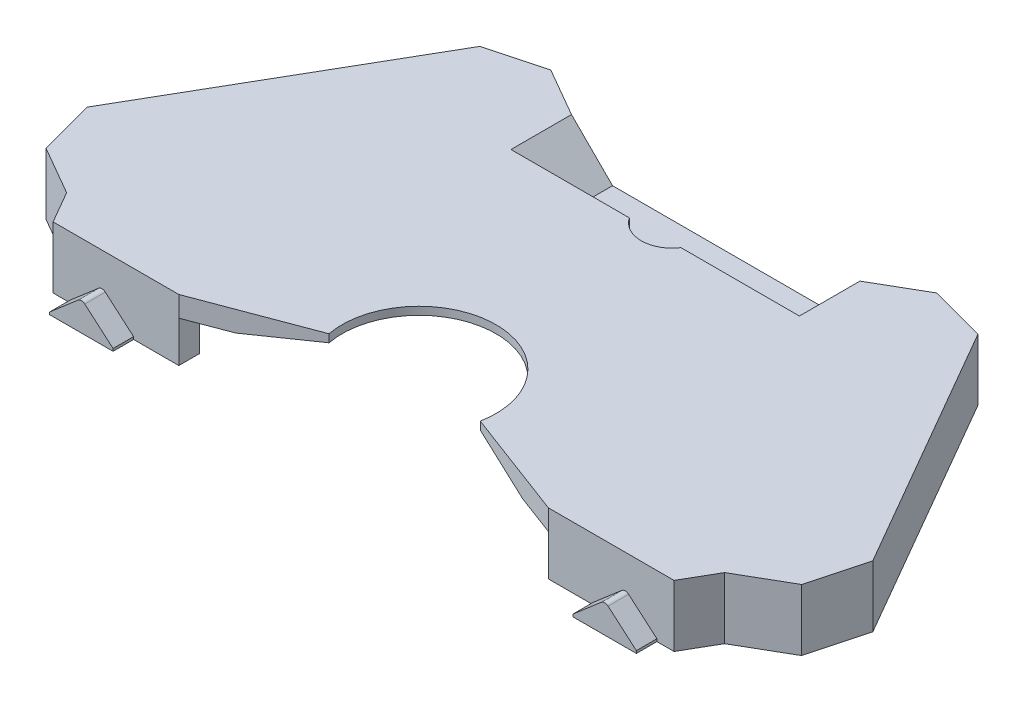
SolidWorks part; units mm, degrees
ref_plane "Front Plane" through (0, 0, 0) normal (0, 0, 1) x (1, 0, 0)
ref_plane "Top Plane" through (0, 0, 0) normal (0, 1, 0) x (1, 0, 0)
ref_plane "Right Plane" through (0, 0, 0) normal (1, 0, 0) x (0, 0, -1)
sketch "Sketch1" plane through (0, 0, 0) normal (0, 1, 0) x (1, 0, 0)
  line L0 (-33, 19.0526) -> (33, 19.0526) construction
  line L1 (33, 19.0526) -> (0, -38.1051) construction
  line L2 (0, -38.1051) -> (-33, 19.0526) construction
  line L3 (-43, 1.7321) -> (-23, 36.3731) construction
  line L4 (23, 36.3731) -> (43, 1.7321) construction
  line L5 (20, -38.1051) -> (-20, -38.1051) construction
  line L6 (-23, 36.3731) -> (-13.5115, 30.8949) construction
  line L7 (-13.5115, 30.8949) -> (13.5115, 30.8949) construction
  line L8 (13.5115, 30.8949) -> (23, 36.3731) construction
  line L9 (-43, 1.7321) -> (-33.5115, -3.7461) construction
  line L10 (-33.5115, -3.7461) -> (-20, -27.1487) construction
  line L11 (-20, -27.1487) -> (-20, -38.1051) construction
  line L12 (20, -38.1051) -> (20, -27.1487) construction
  line L13 (20, -27.1487) -> (33.5115, -3.7461) construction
  line L14 (33.5115, -3.7461) -> (43, 1.7321) construction
  line L15 (0, 26.3949) -> (0, 30.8949) construction
  line L16 (-17, 19.8949) -> (17, 19.8949) construction
  line L17 (-17, 19.8949) -> (-17, -1.1051) construction
  line L18 (17, 19.8949) -> (17, -1.1051) construction
  line L19 (-17, -1.1051) -> (-13, -1.1051) construction
  line L20 (-13, -1.1051) -> (-13, -12.1051) construction
  line L21 (-13, -12.1051) -> (13, -12.1051) construction
  line L22 (13, -12.1051) -> (13, -1.1051) construction
  line L23 (13, -1.1051) -> (17, -1.1051) construction
  line L24 (-27.6088, -13.9699) -> (-18.5155, -8.7199) construction
  line L25 (0, 0) -> (0, 19.0526) construction
  line L26 (-28, 22.3949) -> (-20, 22.3949) construction
  line L27 (-28, 22.3949) -> (-28, -5.6051) construction
  line L28 (-28, -5.6051) -> (-20, -5.6051) construction
  line L29 (-20, 22.3949) -> (-20, -5.6051) construction
  line L34 (28, -5.6051) -> (20, -5.6051) construction
  line L35 (20, 22.3949) -> (20, -5.6051) construction
  line L36 (28, 22.3949) -> (20, 22.3949) construction
  line L37 (28, 22.3949) -> (28, -5.6051) construction
  circle A0 centre (0, 0) radius 19.0526 construction
  circle A1 centre (0, 24.6449) radius 1.75 construction
  circle A2 centre (-17, -7.8449) radius 1.75 construction
  circle A3 centre (17, -7.8449) radius 1.75 construction
  point P4 (0, 19.0526)
  point P13 (0, -38.1051)
  point P15 (-33, 19.0526)
  point P17 (33, 19.0526)
  point P28 (0, 19.8949)
  dimension "D4" = 3.5
  dimension "D1" = 40
  dimension "D2" = 66
  dimension "D3" = 69
  dimension "D5" = 4.5
  dimension "D6" = 11
  dimension "D7" = 34
  dimension "D8" = 21
  dimension "D9" = 26
  dimension "D10" = 32
  dimension "D11" = 10.5
  dimension "D12" = 3
  dimension "D13" = 28
  dimension "D14" = 8
  dimension "D15" = 2.5
sketch "Sketch2" plane through (0, 0, 0) normal (0, 1, 0) x (1, 0, 0)
  line L0 (-17, 19.8949) -> (17, 19.8949) construction
  line L1 (17, 19.8949) -> (17, -1.1051) construction
  line L2 (13, -1.1051) -> (17, -1.1051) construction
  line L3 (13, -12.1051) -> (13, -1.1051) construction
  line L4 (-13, -12.1051) -> (13, -12.1051) construction
  line L5 (-13, -1.1051) -> (-13, -12.1051) construction
  line L6 (-17, -1.1051) -> (-13, -1.1051) construction
  line L7 (-17, 19.8949) -> (-17, -1.1051) construction
  line L8 (-28, -5.6051) -> (-20, -5.6051) construction
  line L9 (-28, 22.3949) -> (-28, -5.6051) construction
  line L10 (-20, 22.3949) -> (-20, -5.6051) construction
  line L11 (-28, 22.3949) -> (-20, 22.3949) construction
  line L12 (28, 22.3949) -> (20, 22.3949) construction
  line L13 (20, 22.3949) -> (20, -5.6051) construction
  line L14 (28, 22.3949) -> (28, -5.6051) construction
  line L15 (28, -5.6051) -> (20, -5.6051) construction
  line L16 (-23, 36.3731) -> (-13.5115, 30.8949) construction
  line L17 (-13.5115, 30.8949) -> (13.5115, 30.8949) construction
  line L18 (13.5115, 30.8949) -> (23, 36.3731) construction
  line L19 (23, 36.3731) -> (43, 1.7321) construction
  line L20 (33.5115, -3.7461) -> (43, 1.7321) construction
  line L21 (20, -27.1487) -> (33.5115, -3.7461) construction
  line L22 (20, -38.1051) -> (20, -27.1487) construction
  line L23 (20, -38.1051) -> (-20, -38.1051) construction
  line L24 (-20, -27.1487) -> (-20, -38.1051) construction
  line L25 (-33.5115, -3.7461) -> (-20, -27.1487) construction
  line L26 (-43, 1.7321) -> (-33.5115, -3.7461) construction
  line L27 (-43, 1.7321) -> (-23, 36.3731) construction
  line L28 (-15.5, 19.8949) -> (15.5, 19.8949)
  line L29 (17, 18.3949) -> (17, 0.3949)
  line L30 (15.1, -1.1051) -> (15.5, -1.1051)
  line L31 (13, -10.6051) -> (13, -3.2051)
  line L32 (-11.5, -12.1051) -> (11.5, -12.1051)
  line L33 (-13, -3.2051) -> (-13, -10.6051)
  line L34 (-15.5, -1.1051) -> (-15.1, -1.1051)
  line L35 (-17, 18.3949) -> (-17, 0.3949)
  line L36 (-26.5, -5.6051) -> (-21.5, -5.6051)
  line L37 (-28, 20.8949) -> (-28, -4.1051)
  line L38 (-20, 20.8949) -> (-20, -4.1051)
  line L39 (-26.5, 22.3949) -> (-21.5, 22.3949)
  line L40 (26.5, 22.3949) -> (21.5, 22.3949)
  line L41 (20, 20.8949) -> (20, -4.1051)
  line L42 (28, 20.8949) -> (28, -4.1051)
  line L43 (26.5, -5.6051) -> (21.5, -5.6051)
  line L44 (-21.5278, 35.5231) -> (-17.65, 33.2842)
  line L45 (-13.5115, 30.8949) -> (13.5115, 30.8949)
  line L46 (17.65, 33.2842) -> (21.5278, 35.5231)
  line L47 (23.85, 34.9008) -> (42.15, 3.2043)
  line L48 (37.65, -1.3568) -> (41.5278, 0.8821)
  line L49 (20, -27.1487) -> (33.5115, -3.7461)
  line L50 (20, -36.4051) -> (20, -31.9275)
  line L51 (18.3, -38.1051) -> (-18.3, -38.1051)
  line L52 (-20, -31.9275) -> (-20, -36.4051)
  line L53 (-33.5115, -3.7461) -> (-20, -27.1487)
  line L54 (-41.5278, 0.8821) -> (-37.65, -1.3568)
  line L55 (-42.15, 3.2043) -> (-23.85, 34.9008)
  line L56 (-13.5115, 30.8949) -> (-16.15, 30.8949)
  line L57 (-17.65, 32.3949) -> (-17.65, 33.2842)
  line L58 (13.5115, 30.8949) -> (16.15, 30.8949)
  line L59 (17.65, 32.3949) -> (17.65, 33.2842)
  line L60 (33.5115, -3.7461) -> (34.8308, -1.4611)
  line L61 (36.8798, -0.9121) -> (37.65, -1.3568)
  line L62 (20, -27.1487) -> (18.6808, -29.4338)
  line L63 (19.2298, -31.4828) -> (20, -31.9275)
  line L64 (-20, -27.1487) -> (-18.6808, -29.4338)
  line L65 (-19.2298, -31.4828) -> (-20, -31.9275)
  line L66 (-33.5115, -3.7461) -> (-34.8308, -1.4611)
  line L67 (-36.8798, -0.9121) -> (-37.65, -1.3568)
  line L68 (-23.85, 34.9008) -> (-21.5278, 35.5231)
  line L69 (-41.5278, 0.8821) -> (-42.15, 3.2043)
  line L70 (-20, -36.4051) -> (-18.3, -38.1051)
  line L71 (20, -36.4051) -> (18.3, -38.1051)
  line L72 (41.5278, 0.8821) -> (42.15, 3.2043)
  line L73 (21.5278, 35.5231) -> (23.85, 34.9008)
  line L74 (-15.1, -1.1051) -> (-13, -3.2051)
  line L75 (13, -3.2051) -> (15.1, -1.1051)
  circle A0 centre (17, -7.8449) radius 1.75 construction
  circle A1 centre (-17, -7.8449) radius 1.75 construction
  circle A2 centre (0, 24.6449) radius 1.75 construction
  circle A3 centre (17, -7.8449) radius 1.75
  circle A4 centre (-17, -7.8449) radius 1.75
  circle A5 centre (0, 24.6449) radius 1.75
  arc A6 (36.8798, -0.9121) -> (34.8308, -1.4611) centre (36.1298, -2.2111) ccw
  arc A7 (19.2298, -31.4828) -> (18.6808, -29.4338) centre (19.9798, -30.1838) cw
  arc A8 (-19.2298, -31.4828) -> (-18.6808, -29.4338) centre (-19.9798, -30.1838) ccw
  arc A9 (-36.8798, -0.9121) -> (-34.8308, -1.4611) centre (-36.1298, -2.2111) cw
  arc A10 (17.65, 32.3949) -> (16.15, 30.8949) centre (16.15, 32.3949) cw
  arc A11 (-17.65, 32.3949) -> (-16.15, 30.8949) centre (-16.15, 32.3949) ccw
  arc A12 (13, -10.6051) -> (11.5, -12.1051) centre (11.5, -10.6051) cw
  arc A13 (-13, -10.6051) -> (-11.5, -12.1051) centre (-11.5, -10.6051) ccw
  arc A14 (15.5, -1.1051) -> (17, 0.3949) centre (15.5, 0.3949) ccw
  arc A15 (-15.5, -1.1051) -> (-17, 0.3949) centre (-15.5, 0.3949) cw
  arc A16 (15.5, 19.8949) -> (17, 18.3949) centre (15.5, 18.3949) cw
  arc A17 (-15.5, 19.8949) -> (-17, 18.3949) centre (-15.5, 18.3949) ccw
  arc A18 (20, -4.1051) -> (21.5, -5.6051) centre (21.5, -4.1051) ccw
  arc A19 (28, -4.1051) -> (26.5, -5.6051) centre (26.5, -4.1051) cw
  arc A20 (26.5, 22.3949) -> (28, 20.8949) centre (26.5, 20.8949) cw
  arc A21 (21.5, 22.3949) -> (20, 20.8949) centre (21.5, 20.8949) ccw
  arc A22 (-28, -4.1051) -> (-26.5, -5.6051) centre (-26.5, -4.1051) ccw
  arc A23 (-21.5, -5.6051) -> (-20, -4.1051) centre (-21.5, -4.1051) ccw
  arc A24 (-20, 20.8949) -> (-21.5, 22.3949) centre (-21.5, 20.8949) ccw
  arc A25 (-26.5, 22.3949) -> (-28, 20.8949) centre (-26.5, 20.8949) ccw
  dimension "D2" = 1.5
  dimension "D3" = 1.5
  dimension "D1" = 35.3
  dimension "D4" = 1.7
  dimension "D5" = 45
  dimension "D6" = 1.7
  dimension "D7" = 45
  dimension "D8" = 1.7
  dimension "D9" = 45
  dimension "D10" = 1.7
  dimension "D11" = 45
  dimension "D12" = 1.7
  dimension "D13" = 45
  dimension "D14" = 1.7
  dimension "D15" = 45
  dimension "D16" = 2.1
  dimension "D17" = 45
  dimension "D18" = 2.1
  dimension "D19" = 45
extrude "Boss-Extrude1" [suppressed] add sketch "Sketch2" along normal blind 6
sketch "Sketch3" [suppressed] plane through (0, 6, 0) normal (0, 1, 0) x (1, 0, 0)
  line L0 (0, 0) -> (0, 28.3949) construction
  line L1 (-19.25, 28.3949) -> (19.25, 28.3949)
  line L2 (-20.75, 26.8949) -> (-20.75, -11.6051)
  line L3 (-19.25, -13.1051) -> (19.25, -13.1051)
  line L4 (20.75, 26.8949) -> (20.75, -11.6051)
  line L5 (16.15, 30.8949) -> (-16.15, 30.8949) construction
  arc A0 (20.75, -11.6051) -> (19.25, -13.1051) centre (19.25, -11.6051) cw
  arc A1 (-20.75, -11.6051) -> (-19.25, -13.1051) centre (-19.25, -11.6051) ccw
  arc A2 (19.25, 28.3949) -> (20.75, 26.8949) centre (19.25, 26.8949) cw
  arc A3 (-19.25, 28.3949) -> (-20.75, 26.8949) centre (-19.25, 26.8949) ccw
  point P15 (20.75, 28.3949)
  point P18 (-20.75, 28.3949)
  dimension "D3" = 1.5
  dimension "D1" = 41.5
  dimension "D2" = 2.5
extrude "Cut-Extrude1" [suppressed] cut sketch "Sketch3" against normal blind 1.4 contours L2 A1 L3 A0 L4 A2 L1 A3
sketch "Sketch4" [suppressed] plane through (0, 0, 0) normal (0, 1, 0) x (1, 0, 0)
  line L0 (28, -5.6051) -> (20, -5.6051) construction
  line L1 (28, 22.3949) -> (28, -5.6051) construction
  line L2 (20, 22.3949) -> (20, -5.6051) construction
  line L3 (28, 22.3949) -> (20, 22.3949) construction
  line L4 (-28, 22.3949) -> (-28, -5.6051) construction
  line L5 (-28, -5.6051) -> (-20, -5.6051) construction
  line L6 (-20, 22.3949) -> (-20, -5.6051) construction
  line L7 (-28, 22.3949) -> (-20, 22.3949) construction
  line L16 (-13.5115, 30.8949) -> (13.5115, 30.8949) construction
  line L17 (13.5115, 30.8949) -> (23, 36.3731) construction
  line L18 (23, 36.3731) -> (43, 1.7321) construction
  line L19 (33.5115, -3.7461) -> (43, 1.7321) construction
  line L20 (20, -27.1487) -> (33.5115, -3.7461) construction
  line L21 (20, -38.1051) -> (20, -27.1487) construction
  line L22 (20, -38.1051) -> (-20, -38.1051) construction
  line L23 (-20, -27.1487) -> (-20, -38.1051) construction
  line L24 (-33.5115, -3.7461) -> (-20, -27.1487) construction
  line L25 (-43, 1.7321) -> (-33.5115, -3.7461) construction
  line L26 (-43, 1.7321) -> (-23, 36.3731) construction
  line L27 (-23, 36.3731) -> (-13.5115, 30.8949) construction
  line L28 (26.6647, -5.6051) -> (20, -5.6051)
  line L29 (28, 17.7128) -> (28, -3.2923)
  line L30 (20, 22.3949) -> (20, -5.6051)
  line L31 (25.2968, 22.3949) -> (20, 22.3949)
  line L32 (-28, 17.7128) -> (-28, -3.2923)
  line L33 (-26.6647, -5.6051) -> (-20, -5.6051)
  line L34 (-20, 22.3949) -> (-20, -5.6051)
  line L35 (-25.2968, 22.3949) -> (-20, 22.3949)
  line L44 (-13.5115, 30.8949) -> (13.5115, 30.8949) construction
  line L45 (13.5115, 30.8949) -> (23, 36.3731) construction
  line L46 (23, 36.3731) -> (43, 1.7321) construction
  line L47 (33.5115, -3.7461) -> (43, 1.7321) construction
  line L48 (20, -27.1487) -> (33.5115, -3.7461) construction
  line L49 (20, -38.1051) -> (20, -27.1487) construction
  line L50 (20, -38.1051) -> (-20, -38.1051) construction
  line L51 (-20, -27.1487) -> (-20, -38.1051) construction
  line L52 (-33.5115, -3.7461) -> (-20, -27.1487) construction
  line L53 (-43, 1.7321) -> (-33.5115, -3.7461) construction
  line L54 (-43, 1.7321) -> (-23, 36.3731) construction
  line L55 (-23, 36.3731) -> (-13.5115, 30.8949) construction
  line L56 (-14.0474, 28.8949) -> (14.0474, 28.8949)
  line L57 (14.0474, 28.8949) -> (18.8038, 31.641)
  line L58 (24.2679, 30.1769) -> (38.2679, 5.9282)
  line L59 (32.0474, -2.282) -> (36.8038, 0.4641)
  line L60 (18.7321, -25.3449) -> (32.0474, -2.282)
  line L64 (-32.0474, -2.282) -> (-18.7321, -25.3449)
  line L65 (-36.8038, 0.4641) -> (-32.0474, -2.282)
  line L66 (-38.2679, 5.9282) -> (-24.2679, 30.1769)
  line L67 (-18.8038, 31.641) -> (-14.0474, 28.8949)
  line L68 (-28, 17.7128) -> (-25.2968, 22.3949)
  line L69 (25.2968, 22.3949) -> (28, 17.7128)
  line L70 (26.6647, -5.6051) -> (28, -3.2923)
  line L71 (-28, -3.2923) -> (-26.6647, -5.6051)
  line L72 (-22.2679, 33.641) -> (-14.0474, 28.8949) construction
  line L73 (-40.2679, 2.4641) -> (-22.2679, 33.641) construction
  line L74 (-24.2679, 30.1769) -> (-18.8038, 31.641)
  line L75 (-40.2679, 2.4641) -> (-32.0474, -2.282) construction
  line L76 (-36.8038, 0.4641) -> (-38.2679, 5.9282)
  line L77 (-18, -26.6128) -> (-18, -36.1051) construction
  line L78 (18, -36.1051) -> (-18, -36.1051) construction
  line L80 (18, -36.1051) -> (18, -26.6128) construction
  line L82 (32.0474, -2.282) -> (40.2679, 2.4641) construction
  line L83 (22.2679, 33.641) -> (40.2679, 2.4641) construction
  line L84 (36.8038, 0.4641) -> (38.2679, 5.9282)
  line L85 (14.0474, 28.8949) -> (22.2679, 33.641) construction
  line L86 (18.8038, 31.641) -> (24.2679, 30.1769)
  line L87 (0, -8) -> (0, 0) construction
  line L88 (-8, 15) -> (8, 15) construction
  line L89 (-8, 15) -> (-8, -8) construction
  line L90 (-8, -8) -> (8, -8) construction
  line L91 (8, 15) -> (8, -8) construction
  line L92 (-8, 19) -> (12, 19)
  line L93 (12, 19) -> (12, 3.5)
  line L94 (-16, 15) -> (-16, 0)
  line L95 (-16, 15) -> (-16, 19)
  line L96 (-16, 19) -> (-8, 19)
  line L97 (-12.5, 0) -> (-16, 0)
  line L98 (0, -5.3449) -> (0, 0) construction
  line L99 (-16, 15) -> (-16, -8) construction
  line L100 (12, 19) -> (12, -8) construction
  line L101 (-19.5, -5.3449) -> (19.5, -5.3449) construction
  line L102 (-19.5, -5.3449) -> (-19.5, -25.3449) construction
  line L103 (-18.7321, -25.3449) -> (18.7321, -25.3449)
  line L104 (19.5, -5.3449) -> (19.5, -25.3449) construction
  line L105 (-17, -6.0949) -> (-17, -5.3449) construction
  line L106 (-18.75, -7.8449) -> (-19.5, -7.8449) construction
  line L107 (-32.0474, -2.282) -> (-18, -26.6128) construction
  line L108 (18, -26.6128) -> (32.0474, -2.282) construction
  circle A0 centre (17, -7.8449) radius 1.75 construction
  circle A1 centre (0, 24.6449) radius 1.75 construction
  circle A2 centre (-17, -7.8449) radius 1.75 construction
  circle A3 centre (17, -7.8449) radius 1.75
  circle A4 centre (0, 24.6449) radius 1.75
  circle A5 centre (-17, -7.8449) radius 1.75
  arc A6 (-12.5, 0) -> (12, 3.5) centre (0, 0) ccw
  dimension "D11" = 25
  dimension "D2" = 3
  dimension "D3" = 3
  dimension "D4" = 5.6569
  dimension "D5" = 45
  dimension "D6" = 45
  dimension "D9" = 45
  dimension "D10" = 45
  dimension "D12" = 16
  dimension "D13" = 23
  dimension "D14" = 8
  dimension "D15" = 4
  dimension "D17" = 39
  dimension "D18" = 20
  dimension "D1" = 2
  dimension "D16" = 8
extrude "Boss-Extrude2" [suppressed] add sketch "Sketch4" against normal blind 2
sketch "Sketch6" [suppressed] plane through (0, 0, 0) normal (0, 1, 0) x (1, 0, 0)
  line L0 (12, 3.5) -> (12, 19) construction
  line L1 (-16, 0) -> (-12.5, 0) construction
  line L2 (-16, 19) -> (-16, 0) construction
  line L3 (12, 19) -> (-16, 19) construction
  line L4 (12, 3.5) -> (12, 19)
  line L5 (-16, 0) -> (-12.5, 0)
  line L6 (-16, 19) -> (-16, 0)
  line L7 (12, 19) -> (-16, 19)
  line L8 (14, 3.7749) -> (14, 21)
  line L9 (14, 21) -> (-18, 21)
  line L10 (-18, 21) -> (-18, -2)
  line L11 (-18, -2) -> (-14.3614, -2)
  arc A0 (-12.5, 0) -> (12, 3.5) centre (0, 0) ccw construction
  arc A1 (-12.5, 0) -> (12, 3.5) centre (0, 0) ccw
  arc A2 (-14.3614, -2) -> (14, 3.7749) centre (0, 0) ccw
  dimension "D1" = 2
extrude "Boss-Extrude3" [suppressed] add sketch "Sketch6" along normal blind 2
chamfer "Chamfer1" [suppressed] distance 0.5 angle 60
sketch "Sketch7" [suppressed] plane through (0, 0, 0) normal (0, 1, 0) x (1, 0, 0)
  line L0 (20, -5.6051) -> (26.6647, -5.6051) construction
  line L1 (-26.6647, -5.6051) -> (-20, -5.6051) construction
  line L2 (20, -5.6051) -> (26.6647, -5.6051)
  line L3 (-26.6647, -5.6051) -> (-20, -5.6051)
  line L4 (-26.6647, -7.6051) -> (-20, -7.6051)
  line L5 (20, -7.6051) -> (26.6647, -7.6051)
  line L6 (-20, -5.6051) -> (-20, -7.6051)
  line L7 (20, -5.6051) -> (20, -7.6051)
  line L8 (-26.6647, -5.6051) -> (-30.1288, -5.6051)
  line L9 (-32.0474, -2.282) -> (-18.7321, -25.3449) construction
  line L10 (-30.1288, -5.6051) -> (-28.9741, -7.6051)
  line L11 (-28.9741, -7.6051) -> (-26.6647, -7.6051)
  line L12 (26.6647, -5.6051) -> (30.1288, -5.6051)
  line L13 (18.7321, -25.3449) -> (32.0474, -2.282) construction
  line L14 (30.1288, -5.6051) -> (28.9741, -7.6051)
  line L15 (28.9741, -7.6051) -> (26.6647, -7.6051)
  dimension "D1" = 2
extrude "Boss-Extrude4" [suppressed] add sketch "Sketch7" along normal blind 6
sketch "Sketch8" [suppressed] plane through (-20, 0, 0) normal (1, 0, 0) x (0, 0, -1)
  line L0 (-7.6051, 6) -> (-7.6051, 0)
  line L1 (-7.6051, 0) -> (-25.3449, 0)
  line L2 (-25.3449, 0) -> (-25.3449, 2)
  line L3 (-25.3449, 2) -> (-7.6051, 6)
  dimension "D1" = 2
extrude "Boss-Extrude5" [suppressed] add sketch "Sketch8" against normal blind 2
sketch "Sketch9" [suppressed] plane through (0, 0, 0) normal (0, -1, 0) x (1, 0, 0)
  line L4 (-22, 25.3449) -> (-22, 19.6846)
  line L5 (-22, 19.6846) -> (-20, 23.1487)
  line L6 (-20, 23.1487) -> (-20, 25.3449)
  line L7 (-20, 25.3449) -> (-22, 25.3449)
  line L8 (-22, 25.3449) -> (-22, 19.6846)
  line L9 (-22, 19.6846) -> (-20, 23.1487)
  line L10 (-20, 23.1487) -> (-20, 25.3449)
  line L11 (-20, 25.3449) -> (-22, 25.3449)
  dimension "D1" = 0
extrude "Cut-Extrude2" [suppressed] cut sketch "Sketch9" against normal through all
sketch "Sketch12" [suppressed] plane through (0, 0, 7.6051) normal (0, 0, 1) x (1, 0, 0)
  line L0 (-25.4871, 6) -> (-25.4871, 0) construction
  line L1 (-28.9741, 6) -> (-22, 6) construction
  line L2 (-28.9741, 0) -> (-22, 0) construction
  line L3 (-25.4871, 3) -> (-28.9741, 0) construction
  line L4 (-25.4871, 3) -> (-22, 0) construction
  line L5 (-25.4871, 3.2638) -> (-22.2, 0.4359)
  line L6 (-25.4871, 3.2638) -> (-28.7741, 0.4359)
  line L10 (-22.2, 0) -> (-28.7741, 0)
  line L11 (-25.4871, 3.2638) -> (-29.1046, 0.1516) construction
  line L12 (-25.4871, 3.2638) -> (-21.8696, 0.1516) construction
  line L15 (-28.7741, 6) -> (-28.7741, 0)
  line L16 (-28.7741, 0.4359) -> (-28.7741, 0)
  line L18 (-22.2, 0) -> (-22.2, 6)
  line L19 (-22.2, 0) -> (-22.2, 0.4359)
  dimension "D1" = 0.2
  dimension "D2" = 0.2
  dimension "D3" = 0.2
extrude "Cut-Extrude4" [suppressed] cut sketch "Sketch12" against normal blind 2
mirror "Mirror1" [suppressed] about plane through (0, 0, 0) normal (1, 0, 0)
fillet "Fillet1" [suppressed] radius 1.5
fillet "Fillet2" [suppressed] radius 0.5
sketch "Sketch13" plane through (0, 0, 0) normal (0, 1, 0) x (1, 0, 0)
  line L2 (-18, 21) -> (-14.0474, 21)
  line L6 (-28, 17.7128) -> (-28, -3.2923)
  line L7 (-25.2968, 22.3949) -> (-28, 17.7128)
  line L8 (-20, 22.3949) -> (-25.2968, 22.3949)
  line L9 (-20, -5.6051) -> (-20, 22.3949)
  line L10 (-26.6647, -5.6051) -> (-20, -5.6051)
  line L11 (-28, -3.2923) -> (-26.6647, -5.6051)
  line L12 (-28, 17.7128) -> (-28, -3.2923) construction
  line L13 (-25.2968, 22.3949) -> (-28, 17.7128) construction
  line L14 (-20, 22.3949) -> (-25.2968, 22.3949) construction
  line L17 (-28, -3.2923) -> (-27.8194, -3.6051) construction
  line L18 (28, -3.2923) -> (28, 17.7128)
  line L19 (28, 17.7128) -> (25.2968, 22.3949)
  line L20 (25.2968, 22.3949) -> (20, 22.3949)
  line L21 (20, 22.3949) -> (20, -5.6051)
  line L22 (20, -5.6051) -> (26.6647, -5.6051)
  line L23 (26.6647, -5.6051) -> (28, -3.2923)
  line L24 (28, -3.2923) -> (28, 17.7128) construction
  line L25 (28, 17.7128) -> (25.2968, 22.3949) construction
  line L26 (25.2968, 22.3949) -> (20, 22.3949) construction
  line L27 (20, 22.3949) -> (20, -3.6051) construction
  line L29 (27.8194, -3.6051) -> (28, -3.2923) construction
  line L30 (12, 3.5) -> (12, 19)
  line L31 (-16, 0) -> (-12.5, 0)
  line L32 (-16, 15) -> (-16, 0)
  line L33 (-16, 19) -> (-16, 15)
  line L34 (-8, 19) -> (-16, 19)
  line L35 (12, 19) -> (-8, 19)
  line L36 (12, 3.5) -> (12, 19) construction
  line L37 (-16, 0) -> (-12.5, 0) construction
  line L38 (-16, 15) -> (-16, 0) construction
  line L39 (-16, 19) -> (-16, 15) construction
  line L40 (-8, 19) -> (-16, 19) construction
  line L41 (12, 19) -> (-8, 19) construction
  line L43 (-18, -5.4051) -> (-18, 21)
  line L44 (20, 22.3949) -> (20, -3.6051) construction
  line L46 (18, -5.4051) -> (18, 21)
  line L48 (-14.0474, 28.8949) -> (-14.0474, 21)
  line L50 (18.7321, -25.3449) -> (32.0474, -2.282)
  line L51 (32.0474, -2.282) -> (36.8038, 0.4641)
  line L52 (36.8038, 0.4641) -> (38.2679, 5.9282)
  line L53 (38.2679, 5.9282) -> (24.2679, 30.1769)
  line L54 (24.2679, 30.1769) -> (18.8038, 31.641)
  line L55 (18.8038, 31.641) -> (14.0474, 28.8949)
  line L56 (14.0474, 28.8949) -> (-14.0474, 28.8949)
  line L57 (-14.0474, 28.8949) -> (-18.8038, 31.641)
  line L58 (-18.8038, 31.641) -> (-24.2679, 30.1769)
  line L59 (-24.2679, 30.1769) -> (-38.2679, 5.9282)
  line L60 (-38.2679, 5.9282) -> (-36.8038, 0.4641)
  line L61 (-36.8038, 0.4641) -> (-32.0474, -2.282)
  line L62 (-32.0474, -2.282) -> (-18.7321, -25.3449)
  line L63 (-18.7321, -25.3449) -> (18.7321, -25.3449)
  line L64 (30.2443, -5.4051) -> (32.0474, -2.282)
  line L65 (32.0474, -2.282) -> (36.8038, 0.4641)
  line L66 (36.8038, 0.4641) -> (38.2679, 5.9282)
  line L67 (38.2679, 5.9282) -> (24.2679, 30.1769)
  line L68 (24.2679, 30.1769) -> (18.8038, 31.641)
  line L69 (18.8038, 31.641) -> (14.0474, 28.8949)
  line L71 (-14.0474, 28.8949) -> (-18.8038, 31.641)
  line L72 (-18.8038, 31.641) -> (-24.2679, 30.1769)
  line L73 (-24.2679, 30.1769) -> (-38.2679, 5.9282)
  line L74 (-38.2679, 5.9282) -> (-36.8038, 0.4641)
  line L75 (-36.8038, 0.4641) -> (-32.0474, -2.282)
  line L76 (-32.0474, -2.282) -> (-30.2443, -5.4051)
  line L78 (-20, -3.6051) -> (-27.8194, -3.6051) construction
  line L79 (-20, -3.6051) -> (-20, 22.3949) construction
  line L80 (20, -3.6051) -> (26.6647, -3.6051) construction
  line L81 (26.6647, -3.6051) -> (27.8194, -3.6051) construction
  line L82 (-20, -5.4051) -> (-30.1288, -5.4051)
  line L83 (-20, -5.4051) -> (-18, -5.4051)
  line L84 (26.6647, -5.4051) -> (30.1288, -5.4051)
  line L85 (20, -5.4051) -> (26.6647, -5.4051)
  line L86 (20, -5.4051) -> (18, -5.4051)
  line L87 (30.1288, -5.4051) -> (30.2443, -5.4051)
  line L88 (-30.1288, -5.4051) -> (-30.2443, -5.4051)
  line L89 (14.0474, 28.8949) -> (14.0474, 21)
  line L90 (14.0474, 21) -> (18, 21)
  circle A1 centre (-17, -7.8449) radius 1.75
  circle A2 centre (-17, -7.8449) radius 1.75 construction
  circle A3 centre (0, 24.6449) radius 1.75
  circle A4 centre (0, 24.6449) radius 1.75 construction
  circle A5 centre (17, -7.8449) radius 1.75
  circle A6 centre (17, -7.8449) radius 1.75 construction
  arc A7 (-12.5, 0) -> (12, 3.5) centre (0, 0) ccw
  arc A8 (-12.5, 0) -> (12, 3.5) centre (0, 0) ccw construction
  dimension "D8" = 2
  dimension "D9" = 2
  dimension "D1" = 0
  dimension "D2" = 0
  dimension "D3" = 0
  dimension "D4" = 0
  dimension "D5" = 0
  dimension "D6" = 0
  dimension "D7" = 0
extrude "Boss-Extrude6" add sketch "Sketch13" along normal blind 2
sketch "Sketch14" plane through (0, 0, 0) normal (0, -1, 0) x (1, 0, 0)
  line L0 (14.0474, -21) -> (18, -21) construction
  line L1 (18, 5.4051) -> (30.2443, 5.4051) construction
  line L2 (30.2443, 5.4051) -> (32.0474, 2.282) construction
  line L3 (32.0474, 2.282) -> (36.8038, -0.4641) construction
  line L4 (36.8038, -0.4641) -> (38.2679, -5.9282) construction
  line L5 (38.2679, -5.9282) -> (24.2679, -30.1769) construction
  line L6 (24.2679, -30.1769) -> (18.8038, -31.641) construction
  line L7 (18.8038, -31.641) -> (14.0474, -28.8949) construction
  line L8 (14.0474, -28.8949) -> (14.0474, -21) construction
  line L9 (-30.2443, 5.4051) -> (-18, 5.4051) construction
  line L10 (-32.0474, 2.282) -> (-30.2443, 5.4051) construction
  line L11 (-36.8038, -0.4641) -> (-32.0474, 2.282) construction
  line L12 (-38.2679, -5.9282) -> (-36.8038, -0.4641) construction
  line L13 (-24.2679, -30.1769) -> (-38.2679, -5.9282) construction
  line L14 (-18.8038, -31.641) -> (-24.2679, -30.1769) construction
  line L15 (-14.0474, -28.8949) -> (-18.8038, -31.641) construction
  line L16 (-14.0474, -21) -> (-14.0474, -28.8949) construction
  line L17 (-18, -21) -> (-14.0474, -21) construction
  line L18 (-30.2443, 5.4051) -> (-18, 5.4051)
  line L19 (-32.0474, 2.282) -> (-30.2443, 5.4051)
  line L20 (-36.8038, -0.4641) -> (-32.0474, 2.282)
  line L21 (-38.2679, -5.9282) -> (-36.8038, -0.4641)
  line L22 (-24.2679, -30.1769) -> (-38.2679, -5.9282)
  line L23 (-18.8038, -31.641) -> (-24.2679, -30.1769)
  line L24 (-14.0474, -28.8949) -> (-18.8038, -31.641)
  line L25 (-14.0474, -21) -> (-14.0474, -28.8949)
  line L26 (-18, -21) -> (-14.0474, -21)
  line L27 (14.0474, -21) -> (18, -21)
  line L28 (14.0474, -28.8949) -> (14.0474, -21)
  line L29 (18.8038, -31.641) -> (14.0474, -28.8949)
  line L30 (24.2679, -30.1769) -> (18.8038, -31.641)
  line L31 (38.2679, -5.9282) -> (24.2679, -30.1769)
  line L32 (36.8038, -0.4641) -> (38.2679, -5.9282)
  line L33 (32.0474, 2.282) -> (36.8038, -0.4641)
  line L34 (30.2443, 5.4051) -> (32.0474, 2.282)
  line L35 (18, 5.4051) -> (30.2443, 5.4051)
  line L36 (-18, -23) -> (-16.0474, -23)
  line L37 (-16.0474, -23) -> (-16.0474, -27.7402)
  line L38 (-16.0474, -27.7402) -> (-19.0864, -29.4948)
  line L39 (-19.0864, -29.4948) -> (-22.9501, -28.4595)
  line L40 (-22.9501, -28.4595) -> (-36.1217, -5.6456)
  line L41 (-36.1217, -5.6456) -> (-35.0864, -1.7819)
  line L42 (-35.0864, -1.7819) -> (-30.5833, 0.8179)
  line L43 (-30.5833, 0.8179) -> (-29.0896, 3.4051)
  line L44 (-29.0896, 3.4051) -> (-18, 3.4051)
  line L45 (18, 3.4051) -> (29.0896, 3.4051)
  line L46 (29.0896, 3.4051) -> (30.5833, 0.8179)
  line L47 (30.5833, 0.8179) -> (35.0864, -1.7819)
  line L48 (35.0864, -1.7819) -> (36.1217, -5.6456)
  line L49 (36.1217, -5.6456) -> (22.9501, -28.4595)
  line L50 (22.9501, -28.4595) -> (19.0864, -29.4948)
  line L51 (19.0864, -29.4948) -> (16.0474, -27.7402)
  line L52 (16.0474, -27.7402) -> (16.0474, -23)
  line L53 (16.0474, -23) -> (18, -23)
  line L54 (-18, -23) -> (-18, -21)
  line L55 (18, -23) -> (18, -21)
  line L56 (-18, 3.4051) -> (-18, 5.4051)
  line L57 (18, 3.4051) -> (18, 5.4051)
  dimension "D1" = 2
extrude "Boss-Extrude7" add sketch "Sketch14" along normal blind 4
sketch "Sketch15" plane through (0, -4, 0) normal (0, -1, 0) x (1, 0, 0)
  line L0 (-14.0474, -21) -> (-14.0474, -28.8949)
  line L1 (-14.0474, -28.8949) -> (-14.0474, -21) construction
  line L2 (-14.0474, -28.8949) -> (14.0474, -28.8949)
  line L3 (14.0474, -28.8949) -> (14.0474, -21)
  line L4 (14.0474, -21) -> (-14.0474, -21)
  circle A0 centre (0, -24.6449) radius 1.75 construction
  circle A1 centre (0, -24.6449) radius 1.75
extrude "Boss-Extrude8" add sketch "Sketch15" against normal blind 2
sketch "Sketch16" plane through (0, 0, 5.4051) normal (0, 0, 1) x (1, 0, 0)
  line L0 (-28.7741, 0) -> (-28.7741, -4) construction
  line L1 (-18, -4) -> (-30.2443, -4) construction
  line L2 (-22.2, 0) -> (-22.2, -4) construction
  line L3 (-28.5741, -3.76) -> (-28.5741, -4)
  line L4 (-22.4, -3.76) -> (-22.4, -4)
  line L5 (-28.7741, 0) -> (-22.2, 0)
  line L6 (-28.7741, 0.4359) -> (-28.7741, 0)
  line L7 (-25.4871, 3.2638) -> (-28.7741, 0.4359)
  line L8 (-22.2, 0.4359) -> (-25.4871, 3.2638)
  line L9 (-22.2, 0) -> (-22.2, 0.4359)
  line L10 (-28.7741, 0) -> (-22.2, 0) construction
  line L11 (-28.7741, 0.4359) -> (-28.7741, 0) construction
  line L12 (-25.4871, 3.2638) -> (-28.7741, 0.4359) construction
  line L13 (-22.2, 0.4359) -> (-25.4871, 3.2638) construction
  line L14 (-22.2, 0) -> (-22.2, 0.4359) construction
  line L15 (-28.5741, -3.76) -> (-25.4871, -1.1041)
  line L16 (-25.4871, -1.1041) -> (-22.4, -3.76)
  line L17 (-28.5741, 0) -> (-28.5741, -4) construction
  line L18 (-22.4, 0) -> (-22.4, -4) construction
  line L19 (-28.5741, -4) -> (-22.4, -4)
  dimension "D4" = 0.4359
  dimension "D5" = 0.24
  dimension "D1" = 0
  dimension "D2" = 0.2
  dimension "D3" = 0.2
extrude "Boss-Extrude9" add sketch "Sketch16" along normal blind 2
fillet "Fillet3" radius 0.5 1 edges at (-25.4871, -1.1041, 6.4051)
mirror "Mirror2" about plane through (0, 0, 0) normal (1, 0, 0) of "Fillet3", "Boss-Extrude9"
sketch "Sketch17" plane through (0, 2, 0) normal (0, 1, 0) x (1, 0, 0)
  line L0 (-18, -5.4051) -> (-7.3672, -1.4051)
  line L1 (-7.3672, -1.4051) -> (7.3672, -1.4051) construction
  line L2 (7.3672, -1.4051) -> (18, -5.4051)
  line L3 (18, -5.4051) -> (18, 21)
  line L4 (18, 21) -> (-18, 21)
  line L5 (-18, 21) -> (-18, -5.4051)
  line L6 (-30.2443, -5.4051) -> (-18, -5.4051) construction
  arc A0 (7.3672, -1.4051) -> (-7.3672, -1.4051) centre (0, 0) ccw
  dimension "D1" = 15
  dimension "D2" = 4
extrude "Boss-Extrude10" add sketch "Sketch17" against normal blind 2
sketch "Sketch18" plane through (0, -2, 0) normal (0, 1, 0) x (1, 0, 0)
  line L0 (14.0474, 21) -> (-14.0474, 21) construction
  line L1 (14.0474, 21) -> (-14.0474, 21)
  line L2 (14.0474, 23) -> (2.5089, 23)
  line L3 (-14.0474, 23) -> (-14.0474, 21)
  line L4 (14.0474, 23) -> (14.0474, 21)
  line L5 (-2.5089, 23) -> (-14.0474, 23)
  line L6 (14.0474, 23) -> (-14.0474, 23) construction
  arc A0 (-2.5089, 23) -> (2.5089, 23) centre (0, 24.6449) ccw
  dimension "D2" = 6
  dimension "D1" = 2
extrude "Boss-Extrude11" add sketch "Sketch18" along normal blind 4
chamfer "Chamfer2" distance 4 angle 45 2 edges at (14.0474, -2, -25.9474) (-14.0474, -2, -25.9474)
fillet "Fillet4" radius 2 12 edges at (29.0896, -2, 3.4051) (30.5833, -2, 0.8179) (-29.0896, -2, 3.4051) (-30.5833, -2, 0.8179) (22.9501, -2, -28.4595) (19.0864, -2, -29.4948) (16.0474, -2, -27.7402) (-22.9501, -2, -28.4595) (-19.0864, -2, -29.4948) (-16.0474, -2, -27.7402) (-16.0474, -2, -23) (16.0474, -2, -23)
chamfer "Chamfer3" distance 7 angle 10 1 edges at (0, 0, -7.5) first distance on face at (0, 0, -12.9181)
